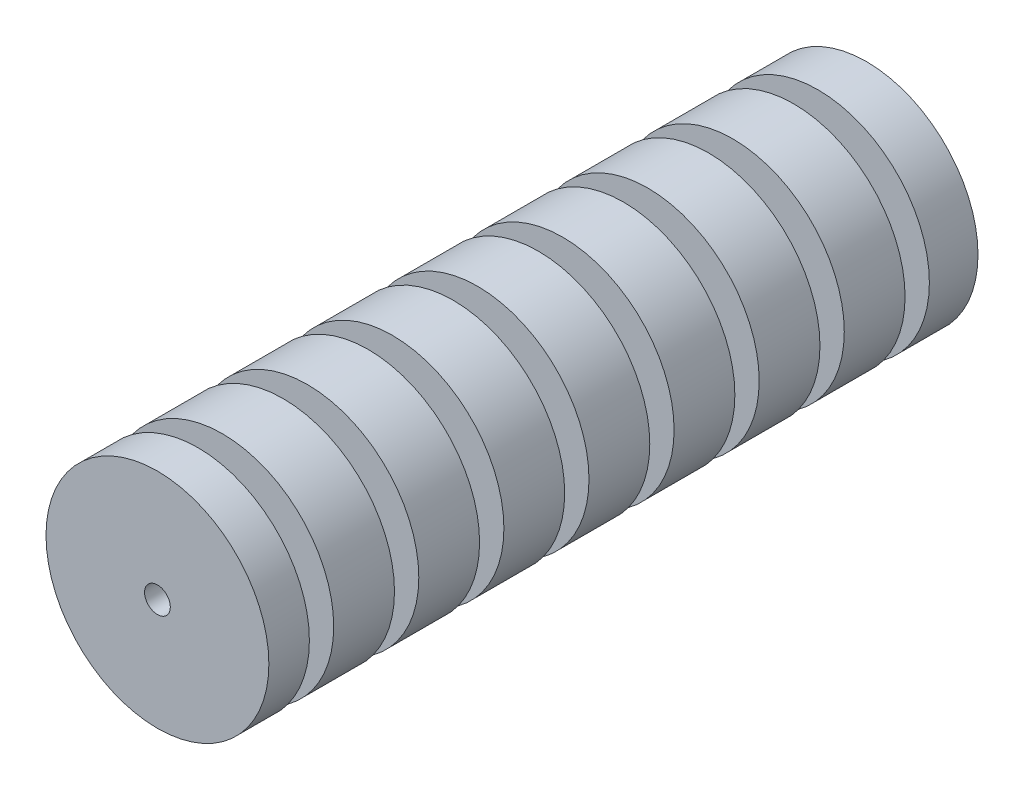
SolidWorks part; units mm, degrees
material "RUBBER 65A"
ref_plane "Front Plane" through (0, 0, 0) normal (0, 0, 1) x (1, 0, 0)
ref_plane "Top Plane" through (0, 0, 0) normal (0, 1, 0) x (1, 0, 0)
ref_plane "Right Plane" through (0, 0, 0) normal (1, 0, 0) x (0, 0, -1)
sketch "Sketch3" plane through (0, 0, 0) normal (0, 0, 1) x (1, 0, 0)
  circle A0 centre (0, 0) radius 27.5
  dimension "D1" = 55
extrude "Boss-Extrude2" add sketch "Sketch3" along normal blind 175
ref_axis "Axis2" through (0, 0, 174.1287) along (0, 0, -1)
sketch "Sketch5" plane through (0, 0, 175) normal (0, 0, 1) x (1, 0, 0)
  circle A0 centre (0, 0) radius 3.175
  dimension "D1" = 6.35
extrude "Cut-Extrude1" cut sketch "Sketch5" against normal through all contours A0
sketch "Sketch4" plane through (0, 0, 0) normal (0, 1, 0) x (1, 0, 0)
  line L0 (0, -175) -> (0, 0) construction
  line L1 (-27.5, -175) -> (27.5, -175) construction
  line L3 (-27.5, -165) -> (-11.5, -165)
  line L4 (-27.5, -165) -> (-27.5, -159)
  line L5 (-27.5, -159) -> (-11.5, -159)
  line L6 (-11.5, -165) -> (-11.5, -159)
  line L63 (-27.5, -144) -> (-27.5, -138)
  line L64 (-27.5, -144) -> (-11.5, -144)
  line L65 (-11.5, -144) -> (-11.5, -138)
  line L66 (-27.5, -138) -> (-11.5, -138)
  line L67 (-27.5, -123) -> (-27.5, -117)
  line L68 (-27.5, -123) -> (-11.5, -123)
  line L69 (-11.5, -123) -> (-11.5, -117)
  line L70 (-27.5, -117) -> (-11.5, -117)
  line L71 (-27.5, -102) -> (-27.5, -96)
  line L72 (-27.5, -102) -> (-11.5, -102)
  line L73 (-11.5, -102) -> (-11.5, -96)
  line L74 (-27.5, -96) -> (-11.5, -96)
  line L75 (-27.5, -81) -> (-27.5, -75)
  line L76 (-27.5, -81) -> (-11.5, -81)
  line L77 (-11.5, -81) -> (-11.5, -75)
  line L78 (-27.5, -75) -> (-11.5, -75)
  line L79 (-27.5, -60) -> (-27.5, -54)
  line L80 (-27.5, -60) -> (-11.5, -60)
  line L81 (-11.5, -60) -> (-11.5, -54)
  line L82 (-27.5, -54) -> (-11.5, -54)
  line L83 (-27.5, -39) -> (-27.5, -33)
  line L84 (-27.5, -39) -> (-11.5, -39)
  line L85 (-11.5, -39) -> (-11.5, -33)
  line L86 (-27.5, -33) -> (-11.5, -33)
  line L87 (-27.5, -18) -> (-27.5, -12)
  line L88 (-27.5, -18) -> (-11.5, -18)
  line L89 (-11.5, -18) -> (-11.5, -12)
  line L90 (-27.5, -12) -> (-11.5, -12)
  line L91 (-27.5, -165) -> (-27.5, -144) construction
  dimension "D1" = 10
  dimension "D2" = 6
  dimension "D3" = 27.5
  dimension "D4" = 16
  dimension "D6" = 21
  dimension "D5" = 8
revolve "Cut-Revolve1" cut sketch "Sketch4" angle 360 about L0
shell "Shell1" thickness 3
sketch "Sketch10" plane through (0, 0, 0) normal (0, 0, -1) x (-1, 0, 0)
  line L0 (0, 27.5) -> (0, -27.5) construction
  line L1 (-27.5, 0) -> (27.5, 0) construction
  line L2 (-1, 27.4818) -> (-1, 3.0134)
  line L3 (1, 3.0134) -> (1, 27.4818)
  line L4 (3.0134, 1) -> (27.4818, 1)
  line L5 (3.0134, -1) -> (27.4818, -1)
  line L6 (-1, -3.0134) -> (-1, -27.4818)
  line L7 (1, -3.0134) -> (1, -27.4818)
  line L8 (-27.4818, -1) -> (-3.0134, -1)
  line L9 (-27.4818, 1) -> (-3.0134, 1)
  circle A0 centre (0, 0) radius 27.5 construction
  circle A1 centre (0, 0) radius 3.175 construction
  arc A2 (-1, -27.4818) -> (1, -27.4818) centre (0, 0) ccw
  arc A3 (27.4818, -1) -> (27.4818, 1) centre (0, 0) ccw
  arc A4 (1, 27.4818) -> (-1, 27.4818) centre (0, 0) ccw
  arc A5 (-27.4818, 1) -> (-27.4818, -1) centre (0, 0) ccw
  arc A6 (-1, -3.0134) -> (1, -3.0134) centre (0, 0) ccw
  arc A7 (-3.0134, 1) -> (-3.0134, -1) centre (0, 0) ccw
  arc A8 (1, 3.0134) -> (-1, 3.0134) centre (0, 0) ccw
  arc A9 (3.0134, -1) -> (3.0134, 1) centre (0, 0) ccw
  dimension "D1" = 1
  dimension "D2" = 1
  dimension "D3" = 1
  dimension "D4" = 1
  dimension "D5" = 1
extrude "Boss-Extrude3" add sketch "Sketch10" against normal up to surface (175 mm away) up to face at (3.175, 0, 175)
sketch "Sketch11" plane through (0, 0, 0) normal (1, 0, 0) x (0, 0, -1)
  line L0 (-117, 27.4818) -> (-117, 1) construction
  line L1 (-165, 30.0791) -> (-159, 30.0791)
  line L2 (-165, 30.0791) -> (-165, 11.4564)
  line L3 (-165, 11.4564) -> (-159, 11.4564)
  line L4 (-159, 30.0791) -> (-159, 11.4564)
  line L5 (-144, 30.0191) -> (-138, 30.0191)
  line L6 (-144, 30.0191) -> (-144, 11.4564)
  line L7 (-144, 11.4564) -> (-138, 11.4564)
  line L8 (-138, 30.0191) -> (-138, 11.4564)
  line L9 (-123, 30.1992) -> (-117, 30.1992)
  line L10 (-123, 30.1992) -> (-123, 11.4755)
  line L11 (-123, 11.4755) -> (-117, 11.4755)
  line L12 (-117, 30.1992) -> (-117, 11.4755)
  line L13 (-117, 11.4564) -> (-117, 1) construction
  line L14 (-75, 11.4564) -> (-75, 1) construction
  line L15 (-102, 30.5593) -> (-96, 30.5593)
  line L16 (-102, 30.5593) -> (-102, 11.4564)
  line L17 (-102, 11.4564) -> (-96, 11.4564)
  line L18 (-96, 30.5593) -> (-96, 11.4564)
  line L19 (-81, 30.9195) -> (-75, 30.9195)
  line L20 (-81, 30.9195) -> (-81, 11.4755)
  line L21 (-81, 11.4755) -> (-75, 11.4755)
  line L22 (-75, 30.9195) -> (-75, 11.4755)
  line L23 (-75, 27.4818) -> (-75, 1) construction
  line L25 (-60, 31.9241) -> (-54, 31.9241)
  line L26 (-60, 31.9241) -> (-60, 11.4564)
  line L27 (-60, 11.4564) -> (-54, 11.4564)
  line L28 (-54, 31.9241) -> (-54, 11.4564)
  line L29 (-39, 30.6232) -> (-33, 30.6232)
  line L30 (-39, 30.6232) -> (-39, 11.4564)
  line L31 (-39, 11.4564) -> (-33, 11.4564)
  line L32 (-33, 30.6232) -> (-33, 11.4564)
  line L33 (-18, 31.5847) -> (-12, 31.5847)
  line L34 (-18, 31.5847) -> (-18, 11.4564)
  line L35 (-18, 11.4564) -> (-12, 11.4564)
  line L36 (-12, 31.5847) -> (-12, 11.4564)
revolve "Cut-Revolve2" cut sketch "Sketch11" angle 360 about axis through (0, 0, 174.1287) along (0, 0, -1)
sketch "Sketch12" plane through (0, 0, 0) normal (0, 1, 0) x (1, 0, 0)
  line L0 (24.4796, -172) -> (6.0935, -172) construction
  line L1 (24.7296, -168) -> (23.4796, -168)
  line L2 (24.7296, -168) -> (24.7296, -172)
  line L3 (24.7296, -172) -> (23.4796, -172)
  line L4 (23.4796, -168) -> (23.4796, -172)
  line L5 (0, 0) -> (0, -175) construction
  line L6 (-3.175, -175) -> (3.175, -175) construction
  line L7 (24.4796, -156) -> (8.441, -156) construction
  line L8 (24.4796, -9) -> (8.441, -9) construction
  line L9 (24.7296, -3) -> (23.4796, -3)
  line L10 (24.7296, -3) -> (24.7296, -9)
  line L11 (24.7296, -9) -> (23.4796, -9)
  line L12 (23.4796, -3) -> (23.4796, -9)
  line L13 (24.7296, -147) -> (23.4796, -147)
  line L14 (24.7296, -147) -> (24.7296, -156)
  line L15 (24.7296, -156) -> (23.4796, -156)
  line L16 (23.4796, -147) -> (23.4796, -156)
  line L17 (24.4796, -135) -> (8.441, -135) construction
  line L18 (24.7296, -126) -> (23.4796, -126)
  line L19 (24.7296, -126) -> (24.7296, -135)
  line L20 (24.7296, -135) -> (23.4796, -135)
  line L21 (23.4796, -126) -> (23.4796, -135)
  line L22 (24.4796, -114) -> (8.441, -114) construction
  line L23 (24.7296, -105) -> (23.4796, -105)
  line L24 (24.7296, -105) -> (24.7296, -114)
  line L25 (24.7296, -114) -> (23.4796, -114)
  line L26 (23.4796, -105) -> (23.4796, -114)
  line L27 (24.4796, -93) -> (8.441, -93) construction
  line L28 (24.7296, -84) -> (23.4796, -84)
  line L29 (24.7296, -84) -> (24.7296, -93)
  line L30 (24.7296, -93) -> (23.4796, -93)
  line L31 (23.4796, -84) -> (23.4796, -93)
  line L32 (24.4796, -72) -> (8.441, -72) construction
  line L33 (24.7296, -63) -> (23.4796, -63)
  line L34 (24.7296, -63) -> (24.7296, -72)
  line L35 (24.7296, -72) -> (23.4796, -72)
  line L36 (23.4796, -63) -> (23.4796, -72)
  line L37 (24.4796, -51) -> (8.441, -51) construction
  line L38 (24.7296, -42) -> (23.4796, -42)
  line L39 (24.7296, -42) -> (24.7296, -51)
  line L40 (24.7296, -51) -> (23.4796, -51)
  line L41 (23.4796, -42) -> (23.4796, -51)
  line L42 (24.4796, -30) -> (8.441, -30) construction
  line L43 (24.7296, -21) -> (23.4796, -21)
  line L44 (24.7296, -21) -> (24.7296, -30)
  line L45 (24.7296, -30) -> (23.4796, -30)
  line L46 (23.4796, -21) -> (23.4796, -30)
  dimension "D1" = 1.25
  dimension "D2" = 1.25
  dimension "D3" = 1.25
  dimension "D4" = 1.25
  dimension "D5" = 1.25
  dimension "D6" = 1.25
  dimension "D7" = 1.25
  dimension "D8" = 1.25
  dimension "D9" = 1.25
revolve "Revolve1" add sketch "Sketch12" angle 360 about L5
ref_plane "Plane1" through (0, 0, 0) normal (-0.7071, -0.7071, 0) x (0, 0, -1)
ref_plane "Plane2" through (0, 0, 0) normal (-0.7071, 0.7071, 0) x (0, 0, -1)
equation "\"inwall\"= .75"
equation "\"outwall\"=2"
